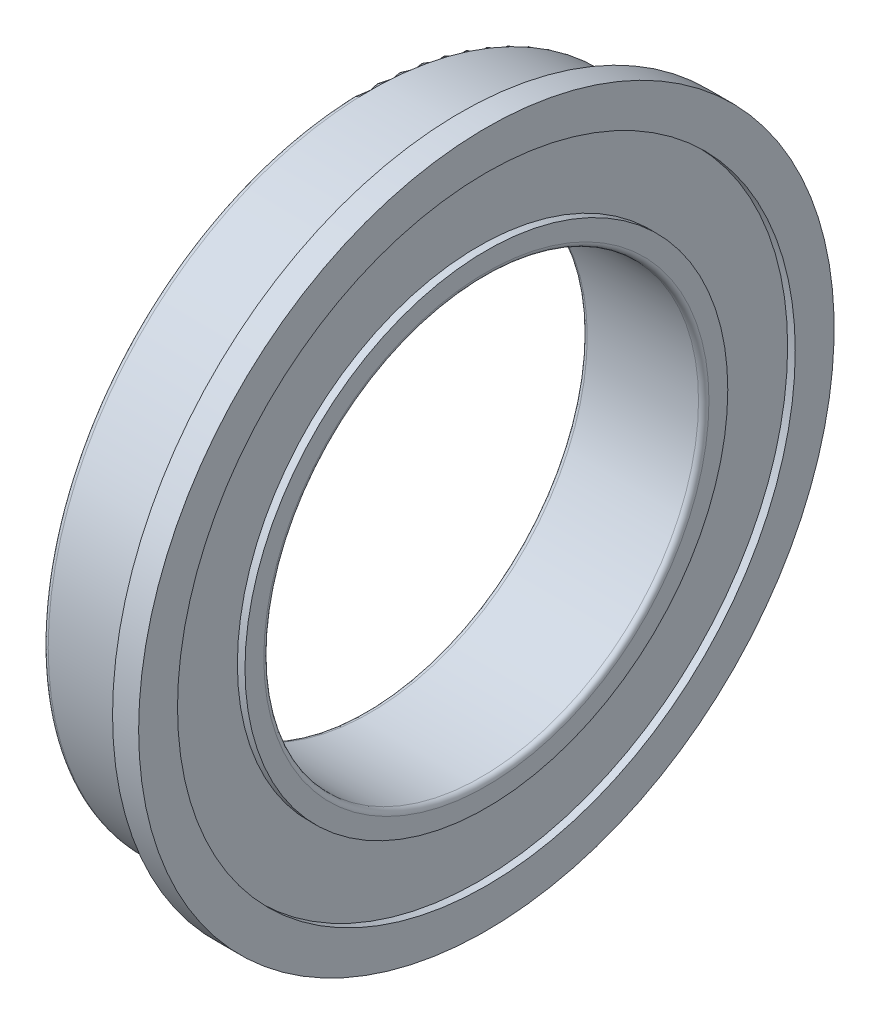
SolidWorks part; units mm, degrees
material "1.4301 (X5CrNi18-10)"
ref_plane "正面" through (0, 0, 0) normal (0, 0, 1) x (1, 0, 0)
ref_plane "平面" through (0, 0, 0) normal (0, 1, 0) x (1, 0, 0)
ref_plane "右側面" through (0, 0, 0) normal (1, 0, 0) x (0, 0, -1)
sketch "ｽｹｯﾁ1" plane through (0, 0, 0) normal (0, 0, 1) x (1, 0, 0)
  line L0 (0, 0) -> (9122.5862, 0) construction
  line L1 (0, 20) -> (-1.5, 20)
  line L2 (-1.5, 20) -> (-1.5, 18.7)
  line L3 (-1.7, 18.5) -> (-7, 18.5)
  line L4 (-7, 18.5) -> (-7, 17.763)
  line L5 (-6.362, 16.923) -> (-4.5198, 16.923)
  line L6 (0, 17.763) -> (0, 20)
  line L7 (-6.362, 14.723) -> (-4.5198, 14.723)
  line L8 (0, 13.883) -> (0, 12.5)
  line L9 (0, 12.5) -> (-7, 12.5)
  line L10 (-7, 12.5) -> (-7, 13.883)
  line L11 (0, 13.883) -> (-0.638, 13.883)
  line L12 (-0.638, 13.883) -> (-0.638, 14.723)
  line L13 (-0.638, 17.763) -> (0, 17.763)
  line L14 (-7, 17.763) -> (-6.362, 17.763)
  line L15 (-6.362, 17.763) -> (-6.362, 16.923)
  line L16 (-6.362, 13.883) -> (-7, 13.883)
  line L17 (-6.362, 14.723) -> (-6.362, 13.883)
  line L18 (-0.638, 16.923) -> (-0.638, 17.763)
  line L19 (-7, 15.823) -> (0, 15.823) construction
  line L20 (-3.5, 12.5) -> (-3.5, 18.5) construction
  line L21 (-2.4802, 16.923) -> (-0.638, 16.923)
  line L22 (-6.362, 13.883) -> (-6.562, 13.883)
  line L23 (-6.362, 13.883) -> (-6.362, 17.763)
  line L24 (-6.362, 17.763) -> (-6.562, 17.763)
  line L25 (-6.562, 13.883) -> (-6.562, 17.763)
  line L26 (-0.638, 13.883) -> (-0.438, 13.883)
  line L27 (-0.638, 13.883) -> (-0.638, 17.763)
  line L28 (-0.638, 17.763) -> (-0.438, 17.763)
  line L29 (-0.438, 13.883) -> (-0.438, 17.763)
  line L30 (-2.4802, 14.723) -> (-0.638, 14.723)
  line L31 (-5, 15.823) -> (-2, 15.823)
  arc A0 (-1.7, 18.5) -> (-1.5, 18.7) centre (-1.5, 18.5) ccw
  circle A1 centre (-3.5, 15.823) radius 1.5 construction
  arc A2 (-4.5198, 16.923) -> (-2.4802, 16.923) centre (-3.5, 15.823) cw
  arc A3 (-4.5198, 14.723) -> (-2.4802, 14.723) centre (-3.5, 15.823) ccw
  arc A4 (-5, 15.823) -> (-2, 15.823) centre (-3.5, 15.823) cw
  dimension "D1" = 7
  dimension "D5" = 0.2
  dimension "D10" = 3
  dimension "D12" = 0.2
  dimension "D2" = 25
  dimension "D3" = 1.5
  dimension "D4" = 40
  dimension "D6" = 37
  dimension "D7" = 35.526
  dimension "D8" = 27.766
  dimension "D9" = 0.438
  dimension "D11" = 0.4
revolve "回転1" add sketch "ｽｹｯﾁ1" angle 360 about L0 region at (-2.9814, 18.0692, 0) region at (-3.5, 13.5201, 0)
revolve "回転3" add sketch "ｽｹｯﾁ1<4>" angle 360 about L19 region at (-3.5, 16.4596, 0)
sketch "ｽｹｯﾁ1<4>" plane through (0, 0, 0) normal (0, 0, 1) x (1, 0, 0) same geometry as "ｽｹｯﾁ1"
pattern_circular "円形ﾊﾟﾀｰﾝ5" count 18 over 360 about axis through (0, 0, 0) along (-1, 0, 0) of bodies 105
revolve "回転2" add sketch "ｽｹｯﾁ1<3>" angle 360 about L0 region at (-0.538, 15.823, 0) region at (-6.462, 15.823, 0)
sketch "ｽｹｯﾁ1<3>" plane through (0, 0, 0) normal (0, 0, 1) x (1, 0, 0) same geometry as "ｽｹｯﾁ1"
fillet "ﾌｨﾚｯﾄ1" radius 0.3 2 edges at (0, 0, 12.5) (-7, 0, 12.5)
fillet "ﾌｨﾚｯﾄ2" radius 0.3 1 edges at (-7, 0, 18.5)
